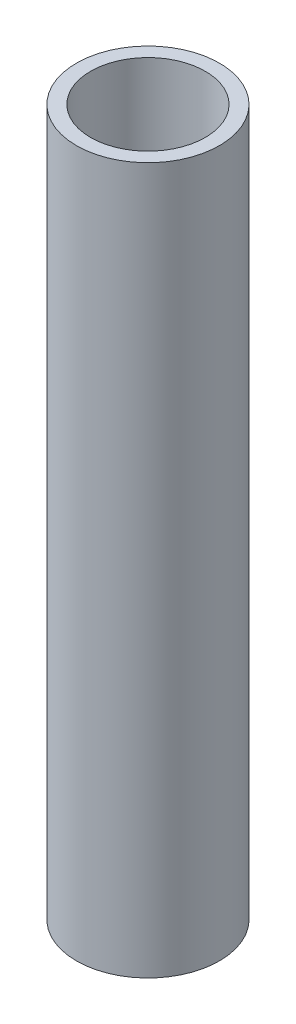
SolidWorks part; units mm, degrees
ref_plane "Front Plane" through (0, 0, 0) normal (0, 0, 1) x (1, 0, 0)
ref_plane "Top Plane" through (0, 0, 0) normal (0, 1, 0) x (1, 0, 0)
ref_plane "Right Plane" through (0, 0, 0) normal (1, 0, 0) x (0, 0, -1)
sketch "Sketch1" plane through (0, 0, 0) normal (0, 1, 0) x (1, 0, 0)
  circle A0 centre (0, 0) radius 4.05
  circle A1 centre (0, 0) radius 3.25
  dimension "D1" = 6.5
  dimension "D2" = 0.8
sketch "Sketch2" plane through (0, 0, 0) normal (0, 1, 0) x (1, 0, 0)
  circle A0 centre (0, 0) radius 3.25 construction
  circle A1 centre (0, 0) radius 4.05 construction
  circle A2 centre (0, 0) radius 3.25
  circle A3 centre (0, 0) radius 4.05
extrude "Boss-Extrude1" add sketch "Sketch2" along normal up to surface (40 mm away)
